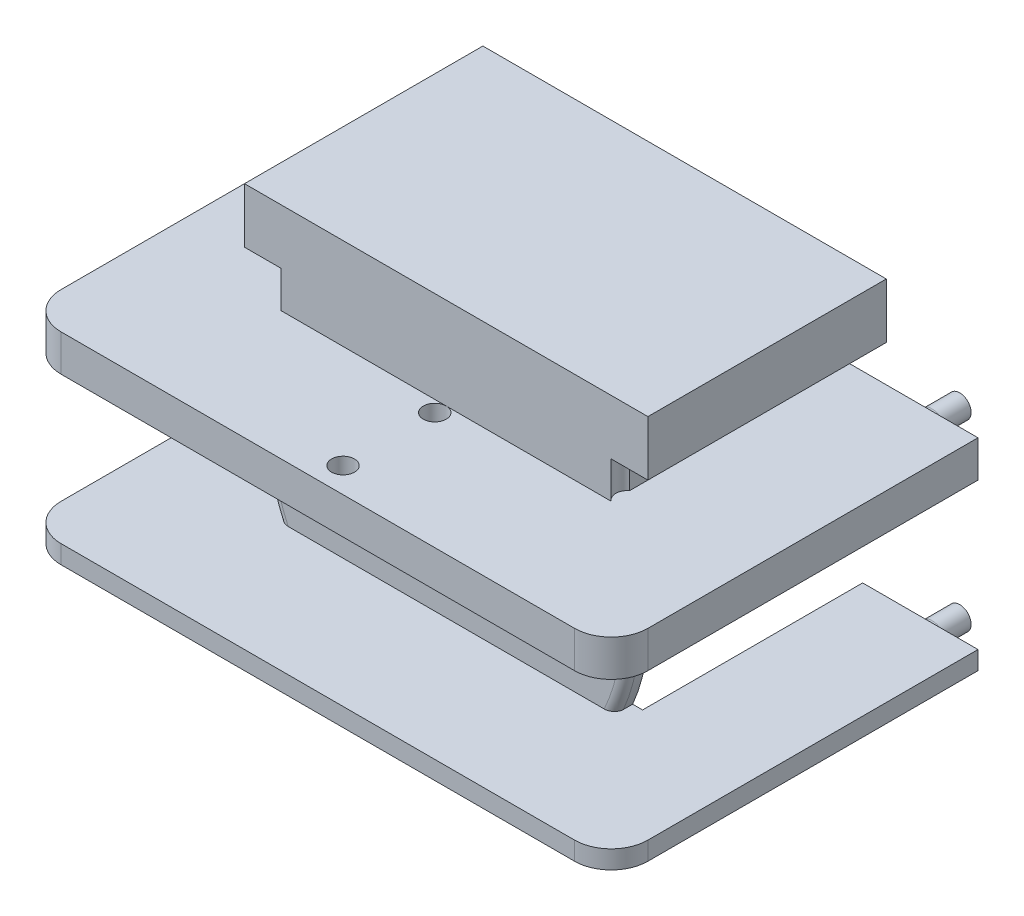
SolidWorks part; units mm, degrees
material "UNOBTANIUM"
ref_plane "Top Plane" through (0, 0, 0) normal (0, 0, 1) x (1, 0, 0)
ref_plane "Right Plane" through (0, 0, 0) normal (0, 1, 0) x (1, 0, 0)
ref_plane "Front Plane" through (0, 0, 0) normal (1, 0, 0) x (0, 0, -1)
ref_axis "x-axis" through (-17.6, 0, 0) along (1, 0, 0)
ref_axis "y-axis" through (0, -9.7375, 0) along (0, 1, 0)
ref_axis "z-axis" through (0, 0, 8.775) along (0, 0, -1)
sketch "Sketch1" plane through (0, 0, 0) normal (0, 0, 1) x (1, 0, 0)
  line L0 (-11, 6) -> (-11, 11)
  line L1 (-11, -6) -> (11, -6)
  line L2 (-11, -6) -> (-11, 6)
  line L3 (-11, 6) -> (11, 6) construction
  line L4 (11, -6) -> (11, 6)
  line L5 (-11, -6) -> (11, 6) construction
  line L6 (-11, 6) -> (11, -6) construction
  line L7 (-11, 11) -> (11, 11)
  line L8 (11, 11) -> (11, 6)
  circle A0 centre (0, 0) radius 9.25 construction
  point P0 (0, 0)
  dimension "D1" = 18.5
  dimension "D2" = 22
  dimension "D3" = 12
  dimension "D4" = 5
extrude "Boss-Extrude1" add sketch "Sketch1" along normal blind 1
sketch "Sketch2" plane through (0, 0, 0) normal (0, 0, -1) x (-1, 0, 0)
  circle A0 centre (0, 0) radius 1.475
  dimension "D1" = 2.95
extrude "Boss-Extrude2" add sketch "Sketch2" along normal blind 14
sketch "Sketch3" plane through (0, 0, 0) normal (0, 0, -1) x (-1, 0, 0)
  line L0 (11, -6) -> (-11, 6) construction
  circle A0 centre (0, 0) radius 3.5
  dimension "D1" = 7
extrude "Boss-Extrude3" add sketch "Sketch3" along normal blind 1
sketch "Sketch4" plane through (0, 0, 0) normal (0, 0, -1) x (-1, 0, 0)
  line L0 (11, -6) -> (-11, -6) construction
  line L1 (11, 11) -> (9, 11)
  line L2 (11, 11) -> (11, -6)
  line L3 (11, -6) -> (9, -6)
  line L4 (9, 11) -> (9, -6)
  line L5 (0, -6) -> (0, 11) construction
  line L7 (-9, 11) -> (-9, -6)
  line L8 (-11, -6) -> (-9, -6)
  line L9 (-11, 11) -> (-11, -6)
  line L10 (-11, 11) -> (-9, 11)
  line L11 (11, 11) -> (-11, 11) construction
  dimension "D1" = 2
extrude "Boss-Extrude4" add sketch "Sketch4" along normal blind 12
sketch "Sketch5" plane through (0, 0, 0) normal (0, 0, -1) x (-1, 0, 0)
  line L0 (-9, -6) -> (-9, 11) construction
  line L1 (9, 11) -> (-9, 11)
  line L2 (9, 11) -> (9, 9)
  line L3 (9, 9) -> (-9, 9)
  line L4 (-9, 11) -> (-9, 9)
  dimension "D1" = 2
extrude "Boss-Extrude5" add sketch "Sketch5" along normal up to surface (12 mm away) up to face at (-10, 2.5, -12)
sketch "Sketch6" plane through (11, 0, 0) normal (1, 0, 0) x (0, 0, -1)
  line L0 (-1, -6) -> (-1, 11) construction
  line L1 (12, -6) -> (-1, -6)
  line L2 (12, -6) -> (12, -4)
  line L3 (12, -4) -> (-1, -4)
  line L4 (-1, -6) -> (-1, -4)
  line L6 (12, 11) -> (12, -6) construction
  line L7 (-1, 6) -> (12, 6)
  line L8 (-1, 6) -> (-1, 4)
  line L9 (-1, 4) -> (12, 4)
  line L10 (12, 6) -> (12, 4)
  line L11 (5.5, 4) -> (5.5, -4) construction
  line L12 (0, 0) -> (5.5, 0) construction
  line L13 (0, -6) -> (0, 6) construction
  point P21 (5.5, 0)
  dimension "D1" = 2
extrude "Boss-Extrude6" add sketch "Sketch6" along normal blind 5
mirror "Mirror1" about plane through (0, 0, 0) normal (1, 0, 0) of "Boss-Extrude6"
sketch "Sketch7" plane through (0, 0, -12) normal (0, 0, -1) x (-1, 0, 0)
  line L0 (-9, -6) -> (-9, 9) construction
  line L1 (-9, 0) -> (-9, 9)
  line L2 (-9, 9) -> (0, 9)
  line L3 (-9, 0) -> (-9, -6)
  line L4 (-9, -6) -> (-6.7082, -6)
  line L5 (11, -6) -> (-11, -6) construction
  arc A0 (0, 9) -> (-6.7082, -6) centre (0, 0) ccw
  line M18 (-9, -6) -> (-9, 9)
  line M19 (-9, 9) -> (9, 9)
extrude "Boss-Extrude7" add sketch "Sketch7" against normal up to surface (12 mm away) contours A0 L4 M18 | A0 M19 M18 region at (8.3306, -4.5409, -12) region at (6.9897, 6.9897, -12) up to face at (3.5, 0, 0)
sketch "Sketch8" plane through (0, 0, -12) normal (0, 0, -1) x (-1, 0, 0)
  line L0 (-11, 4) -> (-9.1652, 4)
  line L1 (-11, 4) -> (-11, -4)
  line L2 (-11, -4) -> (-9.1652, -4)
  arc A1 (-9.1652, 4) -> (-9.1652, -4) centre (0, 0) ccw
  dimension "D1" = 10
extrude "Cut-Extrude1" cut sketch "Sketch8" against normal through all
sketch "Sketch9" plane through (0, 0, -12) normal (0, 0, -1) x (-1, 0, 0)
  line L0 (-16, -4) -> (-9.1652, -4) construction
  line L1 (-8.0623, 4) -> (-11, 4)
  line L2 (-8.0623, 4) -> (-8.0623, -4)
  line L3 (-8.0623, -4) -> (-11, -4)
  line L4 (-11, 4) -> (-11, -4)
  line L5 (-11, -6) -> (-11, 6) construction
  arc A0 (0, 9) -> (-6.7082, -6) centre (0, 0) ccw construction
  arc A1 (0, 9) -> (-6.7082, -6) centre (0, 0) ccw construction
extrude "Cut-Extrude2" cut sketch "Sketch9" against normal up to surface (12 mm away) up to face at (3.5, 0, 0)
mirror "Mirror2" about plane through (0, 0, 0) normal (1, 0, 0) of "Cut-Extrude2", "Cut-Extrude1", "Boss-Extrude7"
sketch "Sketch21" plane through (0, 0, -12) normal (0, 0, -1) x (-1, 0, 0)
  circle A0 centre (0, 0) radius 10.5
  circle A1 centre (0, 0) radius 9 construction
  circle A2 centre (0, 0) radius 3.5 construction
  circle A3 centre (0, 0) radius 3.5
  dimension "D1" = 1.5
extrude "Cut-Extrude11" cut sketch "Sketch21" against normal up to surface (12 mm away) up to face at (0, -0.7091, 0)
sketch "Sketch10" plane through (0, 0, 1) normal (0, 0, 1) x (1, 0, 0)
  line L0 (-16, -4) -> (-16, -6) construction
  line L1 (16, -6) -> (-16, -6)
  line L2 (16, -6) -> (16, -4)
  line L3 (16, -4) -> (-16, -4)
  line L4 (-16, -6) -> (-16, -4)
  line L5 (-16, -4) -> (-9.1652, -4) construction
  line L7 (-16, 6) -> (16, 6)
  line L8 (-16, 6) -> (-16, 4)
  line L9 (-16, 4) -> (16, 4)
  line L10 (16, 6) -> (16, 4)
extrude "Boss-Extrude8" add sketch "Sketch10" along normal blind 7
fillet "Fillet1" radius 0.5 2 edges at (10, 0, 1) (-10, 0, 1)
sketch "Sketch11" plane through (0, 0, -12) normal (0, 0, -1) x (-1, 0, 0)
  line L0 (-16, -5) -> (-13, -5) construction
  line L1 (-16, -6) -> (-16, -4) construction
  circle A0 centre (-13, -5) radius 0.625
  dimension "D1" = 1.25
  dimension "D2" = 3
extrude "Boss-Extrude9" add sketch "Sketch11" along normal blind 2
sketch "Sketch14" plane through (0, 0, -12) normal (0, 0, -1) x (-1, 0, 0)
  line L1 (11, 6) -> (9, 6)
  line L2 (11, 6) -> (11, 8)
  line L3 (11, 8) -> (9, 8)
  line L4 (9, 6) -> (9, 8)
  line L5 (-11, 6) -> (-9, 6)
  line L6 (-11, 6) -> (-11, 8)
  line L7 (-11, 8) -> (-9, 8)
  line L8 (-9, 6) -> (-9, 8)
  dimension "D1" = 18
  dimension "D2" = 2
extrude "Cut-Extrude5" cut sketch "Sketch14" against normal through all
sketch "Sketch12" plane through (0, 0, -12) normal (0, 0, -1) x (-1, 0, 0)
  line L0 (-16, -5) -> (-13, -5) construction
  line L1 (-16, -6) -> (-16, -4) construction
  line L3 (16, -5) -> (13, -5) construction
  line L4 (16, -6) -> (16, -4) construction
  circle A0 centre (13, -5) radius 0.675
  circle A1 centre (-13, -5) radius 0.625 construction
  circle A2 centre (-13, -5) radius 0.625 construction
  dimension "D1" = 1.35
  dimension "D2" = 1.25
extrude "Cut-Extrude3" cut sketch "Sketch12" against normal blind 2.5
sketch "Sketch16" plane through (0, 6, 0) normal (0, 1, 0) x (1, 0, 0)
  line L0 (-9, -1) -> (-9, 12) construction
  line L1 (-9, 0) -> (-9, -1)
  arc A1 (-9, 0) -> (-9, -1) centre (-9.375, -0.5) cw
  dimension "D1" = 0.25
  dimension "D2" = 1
extrude "Cut-Extrude6" cut sketch "Sketch16" along normal blind 2
mirror "Mirror3" about plane through (0, 0, 0) normal (0, 1, 0) of "Boss-Extrude9", "Cut-Extrude3"
mirror "Mirror4" about plane through (0, 0, 0) normal (1, 0, 0) of "Cut-Extrude6"
fillet "Fillet2" radius 0.5 2 edges at (12.375, 5, -12) (13.625, -5, -12)
fillet "Fillet3" radius 0.5 2 edges at (-13.675, 5, -12) (-13.675, -5, -12)
fillet "Fillet4" radius 2 4 edges at (16, -5, 8) (16, 5, 8) (-16, -5, 8) (-16, 5, 8)
sketch "Sketch17" plane through (0, -6, 0) normal (0, -1, 0) x (1, 0, 0)
  line L0 (-16, 6) -> (-16, -12) construction
  line L1 (-14, 8) -> (14, 8) construction
  line L2 (16, 6) -> (16, -12) construction
  line L3 (-16, 6) -> (-16, -12)
  line L4 (-14, 8) -> (14, 8)
  line L5 (16, 6) -> (16, -12)
  line L6 (14.5, 6) -> (14.5, -12)
  line L8 (-14, 6.5) -> (14, 6.5)
  line L9 (-14.5, 6) -> (-14.5, -12)
  line L10 (14.5, -12) -> (16, -12)
  line L11 (-14.5, -12) -> (-16, -12)
  arc A0 (-14, 8) -> (-16, 6) centre (-14, 6) ccw construction
  arc A1 (16, 6) -> (14, 8) centre (14, 6) ccw construction
  arc A2 (-14, 8) -> (-16, 6) centre (-14, 6) ccw
  arc A3 (16, 6) -> (14, 8) centre (14, 6) ccw
  arc A4 (14.5, 6) -> (14, 6.5) centre (14, 6) ccw
  arc A5 (-14, 6.5) -> (-14.5, 6) centre (-14, 6) ccw
  dimension "D1" = 1.5
extrude "Cut-Extrude7" cut sketch "Sketch17" against normal blind 1 and the other way through all
sketch "Sketch19" plane through (0, 6, 0) normal (0, 1, 0) x (1, 0, 0)
  line L0 (9, -1) -> (-9, -1) construction
  line L1 (0, -1.625) -> (0, -1) construction
  line L2 (9, -1) -> (-9, -1) construction
  circle A0 centre (0, -1.625) radius 0.625
  circle A1 centre (0, -6.625) radius 0.625
  point P4 (0, -1)
  dimension "D1" = 1.25
  dimension "D2" = 5
extrude "Cut-Extrude9" cut sketch "Sketch19" against normal up to surface (2 mm away) up to face at (0.0154, 4, -3.1999)
sketch "Sketch20" plane through (0, 0, -12) normal (0, 0, -1) x (-1, 0, 0)
  line L0 (-9, 8) -> (-11, 8) construction
  line L1 (-11, 11) -> (-9, 11)
  line L2 (-11, 11) -> (-11, 8)
  line L3 (-11, 8) -> (-9, 8)
  line L4 (-9, 11) -> (-9, 8)
  line L5 (11, 11) -> (-11, 11) construction
  line L6 (11, 8) -> (9, 8)
  line L7 (11, 8) -> (11, 11)
  line L8 (11, 11) -> (9, 11)
  line L9 (9, 8) -> (9, 11)
  dimension "D1" = 2
equation "\"D1@Sketch12\"=\"D2@Sketch12\"+.1"
